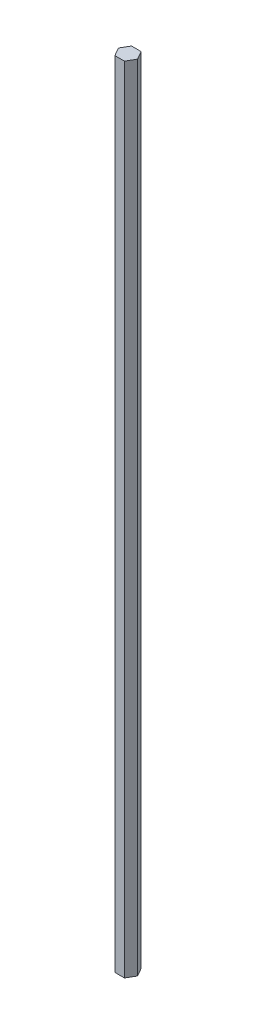
SolidWorks part; units mm, degrees
ref_plane "Front Plane" through (0, 0, 0) normal (0, 0, 1) x (1, 0, 0)
ref_plane "Top Plane" through (0, 0, 0) normal (0, 1, 0) x (1, 0, 0)
ref_plane "Right Plane" through (0, 0, 0) normal (1, 0, 0) x (0, 0, -1)
sketch "Sketch1" plane through (0, 0, 0) normal (0, 1, 0) x (1, 0, 0)
  line L7 (7.3323, 0) -> (3.6662, 6.35)
  line L8 (3.6662, 6.35) -> (-3.6662, 6.35)
  line L9 (-3.6662, 6.35) -> (-7.3323, 0)
  line L10 (-7.3323, 0) -> (-3.6662, -6.35)
  line L11 (-3.6662, -6.35) -> (3.6662, -6.35)
  line L12 (3.6662, -6.35) -> (7.3323, 0)
  circle A0 centre (0, 0) radius 6.35 construction
  dimension "D1" = 12.7
extrude "Boss-Extrude1" add sketch "Sketch1" along normal mid plane 606.552
